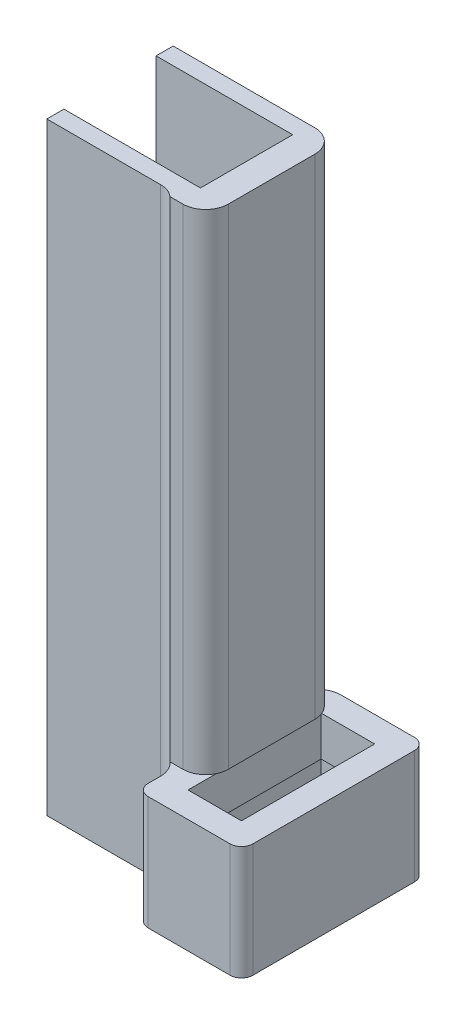
SolidWorks part; units mm, degrees
ref_plane "Alzado" through (0, 0, 0) normal (0, 0, 1) x (1, 0, 0)
ref_plane "Planta" through (0, 0, 0) normal (0, 1, 0) x (1, 0, 0)
ref_plane "Vista lateral" through (0, 0, 0) normal (1, 0, 0) x (0, 0, -1)
sketch "Croquis1" plane through (0, 0, 0) normal (0, 1, 0) x (1, 0, 0)
  line L0 (-1.5, 14.7) -> (7.7, 14.7)
  line L1 (0, 0) -> (6.2, 0)
  line L2 (0, 0) -> (0, 13.2)
  line L3 (0, 13.2) -> (6.2, 13.2)
  line L4 (6.2, 0) -> (6.2, 13.2)
  line L5 (7.7, -1.5) -> (7.7, 14.7)
  line L6 (-1.5, -1.5) -> (7.7, -1.5)
  line L7 (-1.5, -1.5) -> (-1.5, 14.7)
  dimension "D1" = 13.2
  dimension "D2" = 6.2
  dimension "D3" = 1.5
extrude "Saliente-Extruir1" add sketch "Croquis1" along normal blind 10
sketch "Croquis2" plane through (0, 10, 0) normal (0, 1, 0) x (1, 0, 0)
  line L0 (0, 13.2) -> (0, 0) construction
  line L1 (0, 0) -> (6.2, 0) construction
  line L2 (6.2, 0) -> (6.2, 13.2) construction
  line L3 (6.2, 13.2) -> (0, 13.2) construction
  line L4 (0, 13.2) -> (0, 0)
  line L5 (0, 0) -> (6.2, 0)
  line L6 (6.2, 0) -> (6.2, 13.2)
  line L7 (6.2, 13.2) -> (0, 13.2)
  line L8 (5.45, 12.45) -> (0.75, 12.45)
  line L9 (0.75, 12.45) -> (0.75, 0.75)
  line L10 (0.75, 0.75) -> (5.45, 0.75)
  line L11 (5.45, 0.75) -> (5.45, 12.45)
  dimension "D1" = 0.75
extrude "Saliente-Extruir2" add sketch "Croquis2" against normal blind 3.5
sketch "Croquis3" plane through (0, 10, 0) normal (0, 1, 0) x (1, 0, 0)
  line L0 (-1.5, 14.7) -> (-1.5, -1.5) construction
  line L1 (-9.05, 13.7) -> (0.95, 13.7)
  line L3 (-9.05, -1.3) -> (0.95, -1.3)
  line L4 (0.95, 13.7) -> (0.95, -1.3)
  line L5 (7.7, 14.7) -> (-1.5, 14.7) construction
  line L7 (-9.05, 13.7) -> (-9.05, 12.2)
  line L8 (5.45, 0.75) -> (5.45, 12.45) construction
  line L9 (-9.05, 4.1) -> (-9.05, -1.3)
  line L10 (-9.05, 12.2) -> (-1.5, 12.2)
  line L12 (-9.05, 4.1) -> (-1.5, 4.1)
  line L13 (-1.5, 12.2) -> (-1.5, 4.1)
  dimension "D1" = 10
  dimension "D2" = 15
  dimension "D3" = 1
  dimension "D4" = 4.5
  dimension "D5" = 8.1
  dimension "D6" = 1.5
extrude "Saliente-Extruir3" add sketch "Croquis3" along normal blind 43
sketch "Croquis5" plane through (0, 10, 0) normal (0, -1, 0) x (1, 0, 0)
  line L4 (-9.05, -13.7) -> (-1.5, -13.7)
  line L5 (-1.5, -13.7) -> (-1.5, -12.2)
  line L6 (-1.5, -12.2) -> (-9.05, -12.2)
  line L7 (-9.05, -12.2) -> (-9.05, -13.7)
  line L8 (-9.05, -13.7) -> (-1.5, -13.7)
  line L9 (-1.5, -13.7) -> (-1.5, -12.2)
  line L10 (-1.5, -12.2) -> (-9.05, -12.2)
  line L11 (-9.05, -12.2) -> (-9.05, -13.7)
  line L12 (-9.05, -4.1) -> (-1.5, -4.1)
  line L13 (-1.5, -4.1) -> (-1.5, 1.3)
  line L14 (-1.5, 1.3) -> (-9.05, 1.3)
  line L15 (-9.05, 1.3) -> (-9.05, -4.1)
  line L16 (-9.05, -4.1) -> (-1.5, -4.1)
  line L17 (-1.5, -4.1) -> (-1.5, 1.3)
  line L18 (-1.5, 1.3) -> (-9.05, 1.3)
  line L19 (-9.05, 1.3) -> (-9.05, -4.1)
  dimension "D1" = 0
  dimension "D2" = 0
extrude "Saliente-Extruir5" add sketch "Croquis5" along normal up to surface (10 mm away) up to face at (3.1, 0, -6.6)
fillet "Redondeo2" radius 2 1 edges at (-1.5, 5, -14.7)
sketch "Croquis6" plane through (0, 0, 0) normal (0, -1, 0) x (1, 0, 0)
  line L0 (-1.5, -12.2) -> (-1.5, -4.1) construction
  line L1 (-9.05, 1.3) -> (-1.5, 1.3)
  line L2 (-9.05, 1.3) -> (-9.05, -2.6)
  line L3 (-9.05, -2.6) -> (-1.5, -2.6)
  line L4 (-1.5, 1.3) -> (-1.5, -2.6)
  line L5 (-9.05, -4.1) -> (-1.5, -4.1) construction
  dimension "D1" = 1.5
extrude "Cortar-Extruir1" cut sketch "Croquis6" against normal up to surface (53 mm away) up to face at (-4.6625, 53, -7.175)
sketch "Croquis7" plane through (0, 53, 0) normal (0, 1, 0) x (1, 0, 0)
  line L0 (0.95, -1.3) -> (0.95, 13.7) construction
  line L1 (-1.5, -1.3) -> (0.95, -1.3)
  line L2 (-1.5, -1.3) -> (-1.5, 2.1)
  line L3 (-1.5, 2.1) -> (0.95, 2.1)
  line L4 (0.95, -1.3) -> (0.95, 2.1)
  dimension "D1" = 3.4
extrude "Cortar-Extruir2" cut sketch "Croquis7" against normal up to surface (43 mm away) up to face at (2.1415, 10, -6.486)
fillet "Redondeo3" radius 2 3 edges at (-1.5, 26.5, -2.6) (0.95, 31.5, -13.7) (0.95, 31.5, -2.1)
fillet "Redondeo4" radius 1 3 edges at (7.7, 5, -14.7) (7.7, 5, 1.5) (-1.5, 5, 1.5)
sketch "Croquis8" plane through (-9.05, 0, 0) normal (-1, 0, 0) x (0, 0, 1)
  line L4 (-4.1, 0) -> (-2.6, 0)
  line L5 (-2.6, 0) -> (-2.6, 53)
  line L6 (-2.6, 53) -> (-4.1, 53)
  line L7 (-4.1, 53) -> (-4.1, 0)
  line L8 (-4.1, 0) -> (-2.6, 0)
  line L9 (-2.6, 0) -> (-2.6, 53)
  line L10 (-2.6, 53) -> (-4.1, 53)
  line L11 (-4.1, 53) -> (-4.1, 0)
  line L12 (-13.7, 53) -> (-13.7, 0)
  line L13 (-13.7, 0) -> (-12.2, 0)
  line L14 (-12.2, 0) -> (-12.2, 53)
  line L15 (-12.2, 53) -> (-13.7, 53)
  line L16 (-13.7, 53) -> (-13.7, 0)
  line L17 (-13.7, 0) -> (-12.2, 0)
  line L18 (-12.2, 0) -> (-12.2, 53)
  line L19 (-12.2, 53) -> (-13.7, 53)
  dimension "D1" = 0
  dimension "D2" = 0
extrude "Saliente-Extruir6" add sketch "Croquis8" along normal blind 4.45
